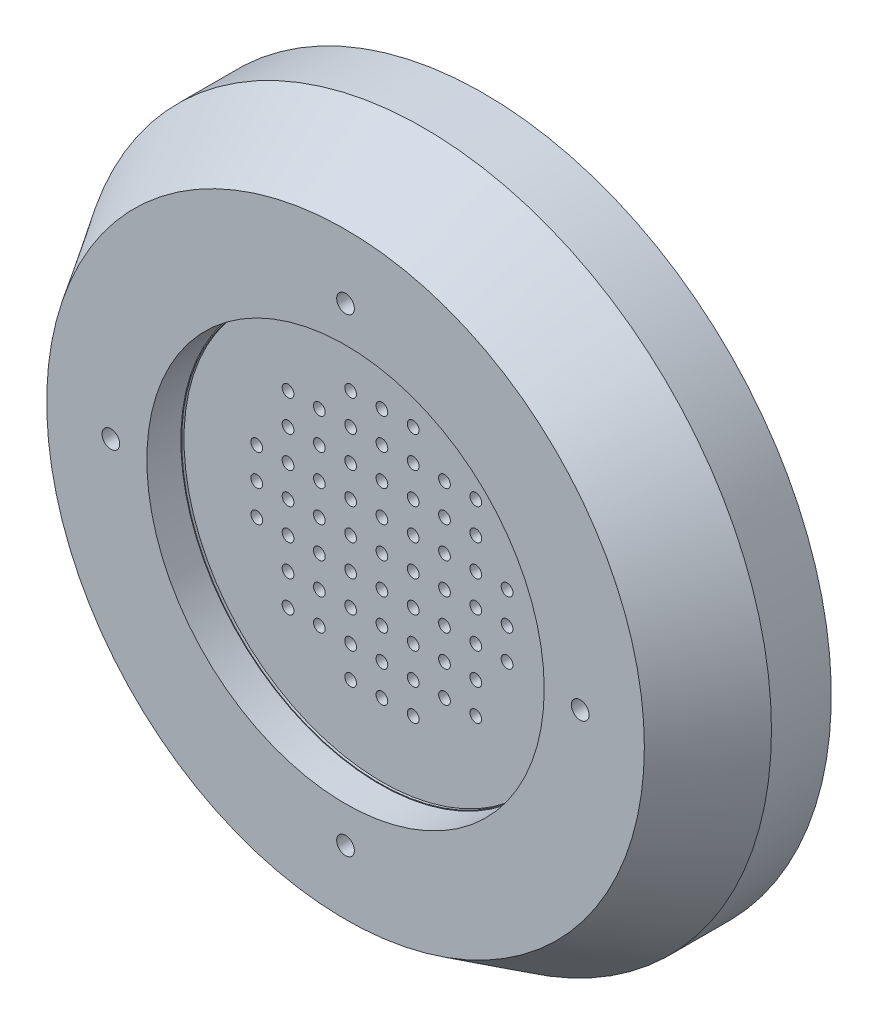
SolidWorks part; units mm, degrees
ref_plane "Plan de face" through (0, 0, 0) normal (0, 0, 1) x (1, 0, 0)
ref_plane "Plan de dessus" through (0, 0, 0) normal (0, 1, 0) x (1, 0, 0)
ref_plane "Plan de droite" through (0, 0, 0) normal (1, 0, 0) x (0, 0, -1)
sketch "Sketch1" plane through (0, 0, 0) normal (0, 0, 1) x (1, 0, 0)
  circle A0 centre (0, 0) radius 44.45
extrude "Boss-Extrude1" add sketch "Sketch1" along normal blind 5
sketch "Sketch2" plane through (0, 0, 5) normal (0, 0, 1) x (1, 0, 0)
  circle A0 centre (0, 0) radius 0.75
extrude "Cut-Extrude1" cut sketch "Sketch2" against normal through all
pattern_linear "LPattern1" count 5 spacing 4 along (0, 1, 0) count 5 spacing 4 along (1, 0, 0) skipping (2, 4), (3, 4), (4, 2), (4, 3), (4, 4) of "Cut-Extrude1"
mirror "Mirror1" about plane through (0, 0, 0) normal (1, 0, 0) of "LPattern1" second plane through (0, 0, 0) second plane normal (0, 1, 0)
sketch "Sketch16" plane through (0, 0, 5) normal (0, 0, 1) x (1, 0, 0)
  circle A0 centre (0, 0) radius 25.4
  circle A1 centre (0, 0) radius 44.45
extrude "Boss-Extrude2" add sketch "Sketch16" along normal blind 4.65
sketch "Sketch17" plane through (0, 0, 0) normal (0, 0, -1) x (-1, 0, 0)
  circle A0 centre (0, 0) radius 39.45
  circle A1 centre (0, 0) radius 44.45
extrude "Boss-Extrude3" add sketch "Sketch17" along normal blind 8
sketch "Sketch34" plane through (0, 0, 0) normal (0, 0, -1) x (-1, 0, 0)
  line L0 (0, -44.45) -> (0, -30)
  circle A0 centre (0, 0) radius 44.45 construction
hole_wizard "#4-40 Tapped Hole2" positions "Sketch35" profile "Sketch36" tap size "#4-40" standard "ANSI Inch" end condition through all
sketch "Sketch35" plane through (0, 0, 0) normal (0, 0, -1) x (-1, 0, 0)
  point P0 (0, -30)
sketch "Sketch36" plane through (0, -30, 0) normal (1, 0, 0) x (0, 1, 0)
  line L0 (0, 0) -> (0, 9.65)
  line L1 (0, 9.65) -> (1.1303, 9.65)
  line L2 (1.1303, 9.65) -> (1.1303, 0)
  line L5 (1.1303, 0) -> (0, 0)
  line L11 (0, -6.35) -> (0, 107.95) construction
  dimension "Thru Tap Drill Dia." = 2.2606
  dimension "Thru Tap Drill Depth" = 9.65
pattern_circular "CirPattern1" count 4 over 360 about axis through (0, 0, 0) along (0, 0, 1) of "#4-40 Tapped Hole2"
sketch "Sketch39" plane through (0, 0, -8) normal (0, 0, -1) x (-1, 0, 0)
  line L0 (0, -44.45) -> (0, -39.45)
  circle A0 centre (0, 0) radius 44.45 construction
  circle A1 centre (0, 0) radius 39.45 construction
hole_wizard "#4-40 Tapped Hole1" positions "Sketch40" profile "Sketch41" tap size "#4-40" standard "ANSI Inch"
sketch "Sketch40" plane through (0, 0, -8) normal (0, 0, -1) x (-1, 0, 0)
  line L0 (0, -44.45) -> (0, -39.45) construction
  point P0 (0, -41.95)
sketch "Sketch41" plane through (0, -41.95, -8) normal (1, 0, 0) x (0, 1, 0)
  line L0 (0, 0) -> (0, 5.6792)
  line L1 (0, 5.6792) -> (1.1303, 5)
  line L2 (1.1303, 5) -> (1.1303, 0)
  line L5 (1.1303, 0) -> (0, 0)
  line L10 (0, 5.6792) -> (-1.1303, 5) construction
  line L11 (0, -6.35) -> (0, 107.95) construction
  dimension "Tap Drill Dia." = 2.2606
  dimension "Tap Drill Depth" = 5
  dimension "Drill Angle" = 118
pattern_circular "CirPattern2" count 3 over 360 about axis through (0, 0, 0) along (0, 0, 1) of "#4-40 Tapped Hole1"
sketch "Sketch43" plane through (0, 0, 5) normal (0, 0, 1) x (1, 0, 0)
  circle A0 centre (0, 0) radius 25.3
  circle A1 centre (0, 0) radius 26.3
extrude "Boss-Extrude4" add sketch "Sketch43" along normal blind 0.3
chamfer "Chamfer1" distance 10 angle 32 1 edges at (44.45, 0, 9.65) first distance on face at (44.45, 0, 9.65)
